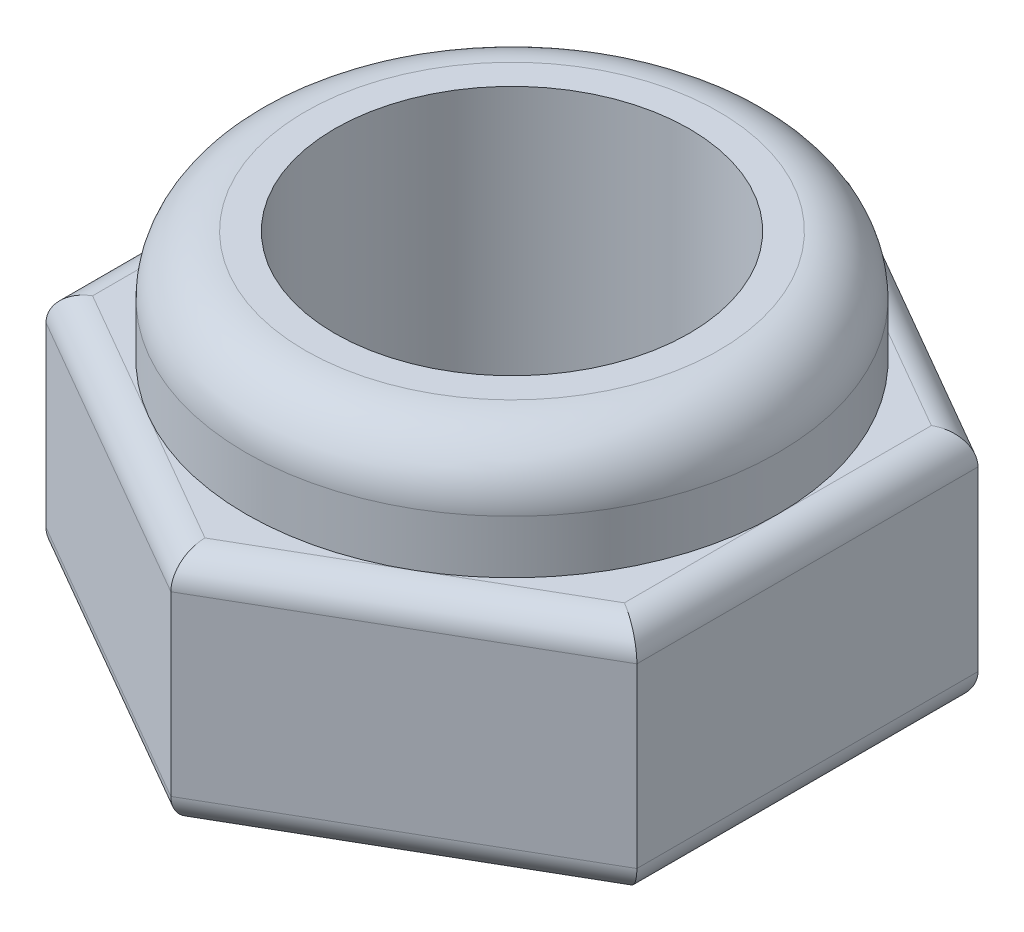
SolidWorks part; units mm, degrees
ref_plane "前视基准面" through (0, 0, 0) normal (0, 0, 1) x (1, 0, 0)
ref_plane "上视基准面" through (0, 0, 0) normal (0, 1, 0) x (1, 0, 0)
ref_plane "右视基准面" through (0, 0, 0) normal (1, 0, 0) x (0, 0, -1)
other "Configuration Table"
sketch "草图1" plane through (0, 0, 0) normal (0, 1, 0) x (1, 0, 0)
  line L1 (0, -5.7735) -> (5, -2.8868)
  line L2 (5, -2.8868) -> (5, 2.8868)
  line L3 (5, 2.8868) -> (0, 5.7735)
  line L4 (0, 5.7735) -> (-5, 2.8868)
  line L5 (-5, 2.8868) -> (-5, -2.8868)
  line L6 (-5, -2.8868) -> (0, -5.7735)
  circle A0 centre (0, 0) radius 5 construction
  point P1 (0, 0)
  dimension "D1" = 10
extrude "凸台-拉伸1" add sketch "草图1" along normal blind 4
sketch "草图2" plane through (0, 4, 0) normal (0, 1, 0) x (1, 0, 0)
  circle A0 centre (0, 0) radius 4.5
  dimension "D1" = 9
extrude "凸台-拉伸2" add sketch "草图2" along normal blind 1.9
sketch "草图3" plane through (0, 5.9, 0) normal (0, 1, 0) x (1, 0, 0)
  circle A0 centre (0, 0) radius 3
  dimension "D1" = 6
extrude "切除-拉伸1" cut sketch "草图3" against normal blind 20
fillet "圆角1" radius 1 1 edges at (0, 5.9, 4.5)
fillet "圆角3" radius 0.5 12 edges at (-2.5, 4, -4.3301) (2.5, 4, -4.3301) (5, 4, 0) (2.5, 4, 4.3301) (-2.5, 4, 4.3301) (-5, 4, 0) (2.5, 0, 4.3301) (5, 0, 0) (2.5, 0, -4.3301) (-2.5, 0, -4.3301) (-5, 0, 0) (-2.5, 0, 4.3301)
